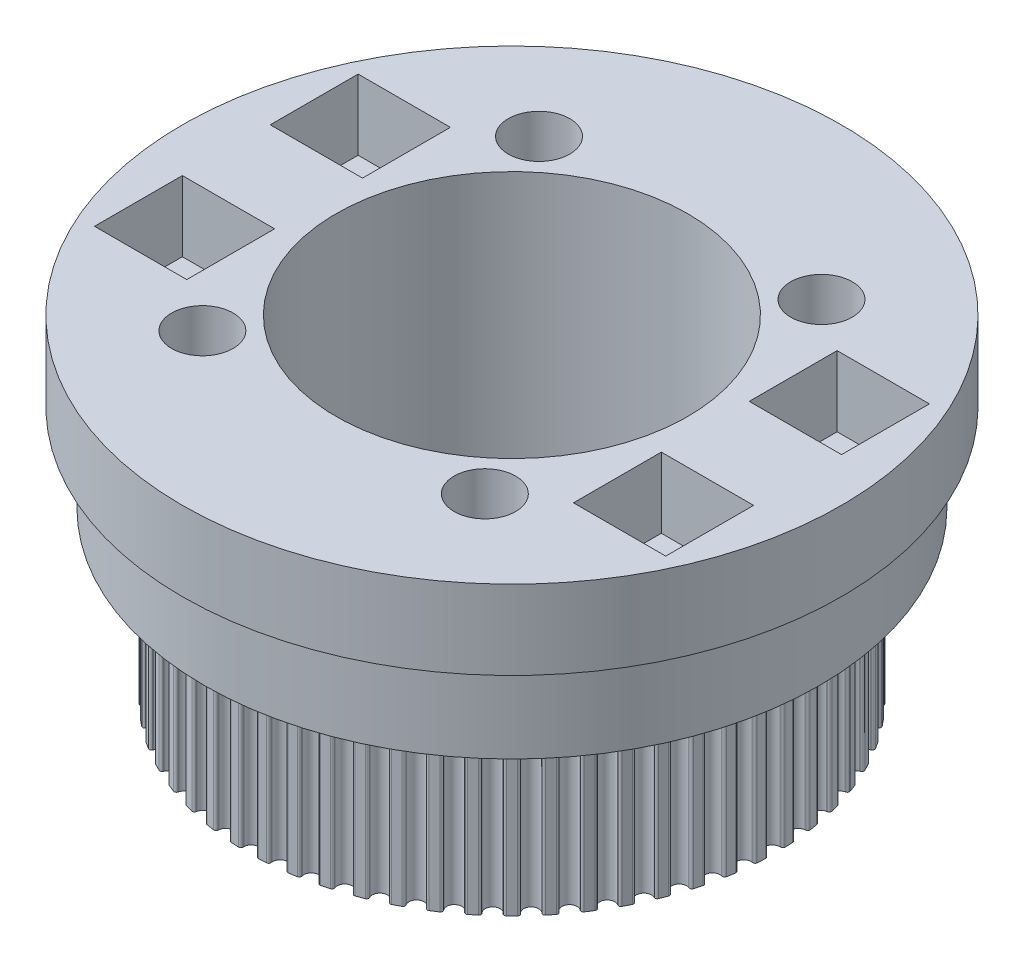
SolidWorks part; units mm, degrees
ref_plane "Front Plane" through (0, 0, 0) normal (0, 0, 1) x (1, 0, 0)
ref_plane "Top Plane" through (0, 0, 0) normal (0, 1, 0) x (1, 0, 0)
ref_plane "Right Plane" through (0, 0, 0) normal (1, 0, 0) x (0, 0, -1)
sketch "Sketch1" plane through (0, 0, 0) normal (0, 1, 0) x (1, 0, 0)
  circle A0 centre (0, 0) radius 37.5
  dimension "D1" = 75
extrude "Boss-Extrude1" add sketch "Sketch1" along normal blind 9
sketch "Sketch3" plane through (0, 9, 0) normal (0, 1, 0) x (1, 0, 0)
  line L0 (-22, -997.1057) -> (-22, 49002.8943) construction
  line L1 (22, -1000.5789) -> (22, 48999.4211) construction
  line L2 (-32.5, -1023.9262) -> (-32.5, 48976.0738) construction
  line L3 (32.5, -1023.3474) -> (32.5, 48976.6526) construction
  line L5 (-22, 5) -> (-32.5, 5)
  line L6 (-22, 5) -> (-22, 15)
  line L7 (-22, 15) -> (-32.5, 15)
  line L8 (-32.5, 5) -> (-32.5, 15)
  line L9 (22, 15) -> (32.5, 15)
  line L10 (22, 15) -> (22, 5)
  line L11 (22, 5) -> (32.5, 5)
  line L12 (32.5, 15) -> (32.5, 5)
  line L13 (-22, -5) -> (-32.5, -5)
  line L14 (-22, -5) -> (-22, -15)
  line L15 (-22, -15) -> (-32.5, -15)
  line L16 (-32.5, -5) -> (-32.5, -15)
  line L17 (22, -5) -> (32.5, -5)
  line L18 (22, -5) -> (22, -15)
  line L19 (22, -15) -> (32.5, -15)
  line L20 (32.5, -5) -> (32.5, -15)
  dimension "D1" = 44
  dimension "D2" = 22
  dimension "D3" = 32.5
  dimension "D4" = 65
  dimension "D5" = 5
  dimension "D6" = 10
  dimension "D7" = 10
  dimension "D8" = 10
  dimension "D9" = 10
  dimension "D10" = 10
  dimension "D11" = 10
  dimension "D12" = 5
extrude "Cut-Extrude2" cut sketch "Sketch3" against normal blind 8
sketch "Sketch4" plane through (0, 0, 0) normal (0, -1, 0) x (1, 0, 0)
  circle A0 centre (0, 0) radius 35
  dimension "D1" = 70
extrude "Boss-Extrude2" add sketch "Sketch4" along normal blind 10
sketch "Sketch5" plane through (0, -10, 0) normal (0, -1, 0) x (1, 0, 0)
  circle A0 centre (0, 0) radius 30
  dimension "D1" = 60
extrude "Boss-Extrude3" add sketch "Sketch5" along normal blind 19
sketch "Sketch2" plane through (0, 9, 0) normal (0, 1, 0) x (1, 0, 0)
  line L0 (-1000, 0) -> (49000, 0) construction
  line L1 (-508.0788, -605.5047) -> (24895.8609, 29669.7317) construction
  line L2 (-642.7876, 766.0444) -> (31496.5929, -37536.1777) construction
  circle A0 centre (0, 0) radius 25 construction
  circle A1 centre (-16.0697, 19.1511) radius 2.6
  circle A2 centre (-16.0697, -19.1511) radius 2.6
  circle A3 centre (16.0697, -19.1511) radius 2.6
  circle A4 centre (16.0697, 19.1511) radius 2.6
  dimension "D1" = 50
  dimension "D2" = 5.2
  dimension "D3" = 5.2
  dimension "D4" = 5.2
  dimension "D5" = 5.2
  dimension "D6" = 50
  dimension "D7" = 80
extrude "Cut-Extrude1" cut sketch "Sketch2" against normal through all
sketch "Sketch6" plane through (0, 9, 0) normal (0, 1, 0) x (1, 0, 0)
  circle A0 centre (-16.0697, 19.1511) radius 3.5
  circle A1 centre (16.0697, 19.1511) radius 3.5
  circle A2 centre (16.0697, -19.1511) radius 3.5
  circle A3 centre (-16.0697, -19.1511) radius 3.5
  dimension "D1" = 7
  dimension "D2" = 7
  dimension "D3" = 7
  dimension "D4" = 7
extrude "Cut-Extrude3" cut sketch "Sketch6" against normal blind 10
sketch "Sketch8" plane through (0, -29, 0) normal (0, -1, 0) x (1, 0, 0)
  circle A0 centre (0, 0) radius 20
  dimension "D1" = 40
extrude "Cut-Extrude4" cut sketch "Sketch8" against normal through all
sketch "Sketch9" plane through (0, -29, 0) normal (0, -1, 0) x (1, 0, 0)
  line L0 (0, 30.638) -> (0, 29.638) construction
  line L1 (0.858, 30.638) -> (0.858, 29.638)
  line L2 (-0.858, 30.638) -> (-0.858, 29.638)
  line L3 (-1000, 28.78) -> (49000, 28.78) construction
  line L4 (-1000, 30) -> (49000, 30) construction
  arc A0 (0.858, 30.638) -> (-0.858, 30.638) centre (0, 30.638) ccw
  arc A1 (-0.858, 29.638) -> (0.858, 29.638) centre (0, 29.638) ccw
  circle A4 centre (0, 0) radius 30 construction
  point P3 (0, 30.138)
  point P13 (0, 28.78)
  dimension "D1" = 0.858
  dimension "D2" = 1.22
  dimension "D3" = 1
extrude "Cut-Extrude5" cut sketch "Sketch9" against normal up to surface (19 mm away) up to face at (0, -10, -35)
fillet "Fillet1" radius 0.25 2 edges at (-0.858, -19.5, 29.9877) (0.858, -19.5, 29.9877)
pattern_circular "CirPattern1" count 60 over 360 about axis through (0, -29, 0) along (0, -1, 0) of "Cut-Extrude5", "Fillet1"
